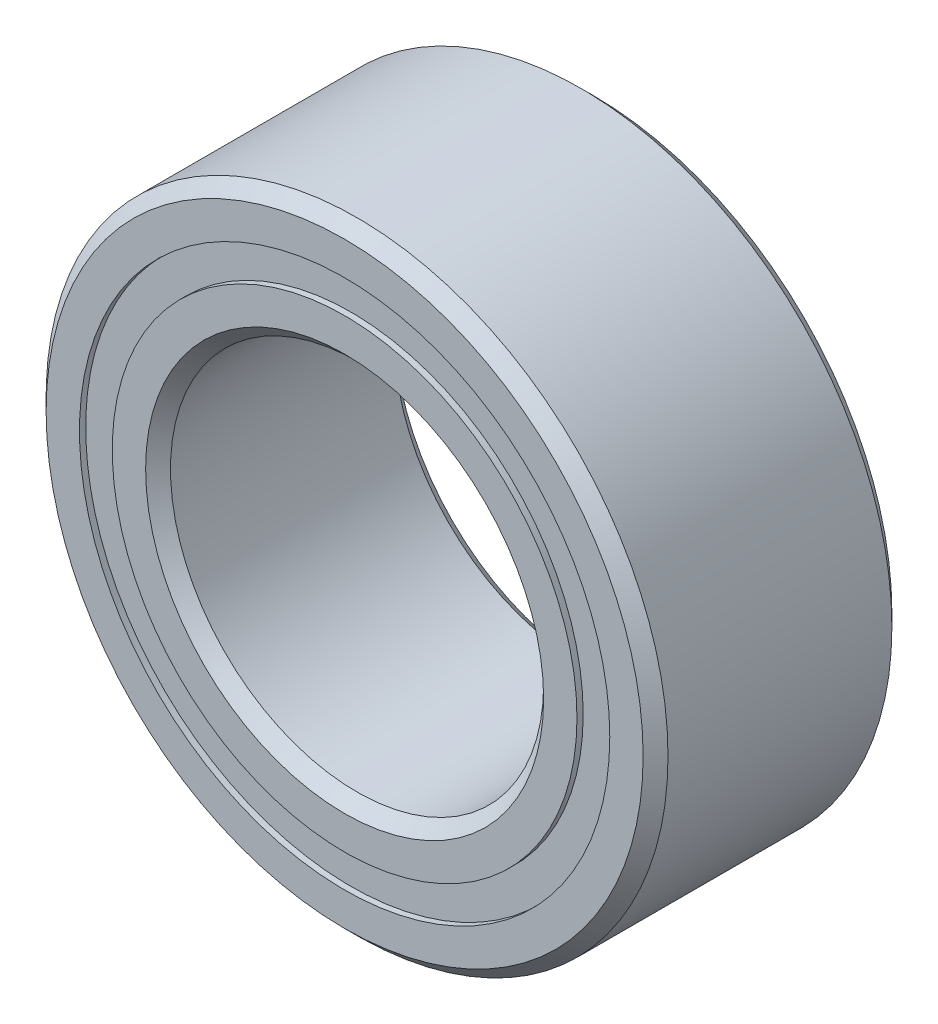
SolidWorks part; units mm, degrees
material "Cast Alloy Steel"
ref_plane "Front Plane" through (0, 0, 0) normal (0, 0, 1) x (1, 0, 0)
ref_plane "Top Plane" through (0, 0, 0) normal (0, 1, 0) x (1, 0, 0)
ref_plane "Right Plane" through (0, 0, 0) normal (1, 0, 0) x (0, 0, -1)
sketch "Sketch1" plane through (0, 0, 0) normal (1, 0, 0) x (0, 0, -1)
  line L0 (-1.5875, 0) -> (1.5875, 0) construction
  line L1 (0, 3.9688) -> (0, -3.9688) construction
  line L2 (1.4288, 3.9687) -> (-1.4288, 3.9687)
  line L3 (-1.4288, 3.9687) -> (-1.5875, 3.81)
  line L4 (-1.5875, 3.81) -> (-1.5875, 3.3843)
  line L5 (-1.5875, 3.3843) -> (-0.7056, 3.3843)
  line L6 (1.5875, 3.3843) -> (0.7056, 3.3843)
  line L7 (1.5875, 3.81) -> (1.5875, 3.3843)
  line L8 (1.4288, 3.9687) -> (1.5875, 3.81)
  line L9 (0, 3.9688) -> (0, 3.175) construction
  line L10 (0, 3.175) -> (0, 2.3813) construction
  arc A0 (-0.7056, 3.3843) -> (0.7056, 3.3843) centre (0, 3.175) cw
  point P14 (0, 2.3813)
  dimension "D3" = 1.4111
  dimension "D1" = 45
  dimension "Width" = 3.175
  dimension "OD" = 7.9375
  dimension "D2" = 0.1588
  dimension "Shaft Dia" = 4.7625
  dimension "D4" = 0.2093
revolve "Revolve1" add sketch "Sketch1" angle 360 about L0
sketch "Sketch3" plane through (0, 0, 0) normal (1, 0, 0) x (0, 0, -1)
  line L0 (-0.7056, 2.9657) -> (-1.5875, 2.9657)
  line L1 (-1.5875, 3.81) -> (-1.5875, 3.3843) construction
  line L2 (-1.4288, 3.9687) -> (-1.5875, 3.81) construction
  line L3 (-1.5875, 2.9657) -> (-1.5875, 2.54)
  line L5 (-1.5875, 2.54) -> (-1.4288, 2.3812)
  line L6 (-1.4288, 2.3812) -> (1.4288, 2.3813)
  line L7 (1.4288, 3.9687) -> (1.4288, -3.9687) construction
  line L8 (1.4288, 2.3813) -> (1.5875, 2.54)
  line L9 (1.5875, -3.81) -> (1.5875, 3.81) construction
  line L10 (1.5875, 2.54) -> (1.5875, 2.9657)
  line L11 (1.5875, 2.9657) -> (0.7056, 2.9657)
  line L12 (0, 3.9688) -> (0, -3.9688) construction
  line L13 (1.4288, 3.9687) -> (1.5875, 3.81) construction
  arc A1 (0.7056, 2.9657) -> (-0.7056, 2.9657) centre (0, 3.175) cw
  arc A2 (0.7056, 3.3843) -> (-0.7056, 3.3843) centre (0, 3.175) ccw construction
revolve "Revolve3" add sketch "Sketch3" angle 360 about L0
sketch "Sketch4" plane through (0, 0, 0) normal (1, 0, 0) x (0, 0, -1)
  line L0 (-0.736, 3.175) -> (0.736, 3.175)
  arc A2 (-0.736, 3.175) -> (0.736, 3.175) centre (0, 3.175) cw
  arc A3 (0.7056, 3.3843) -> (-0.7056, 3.3843) centre (0, 3.175) ccw construction
revolve "Revolve4" add sketch "Sketch4" angle 360 about L0
ref_axis "Axis1" through (0, 0, -1.5875) along (0, 0, 1)
pattern_circular "CirPattern1" count 12 every 30 about axis through (0, 0, -1.5875) along (0, 0, 1) of bodies 104
sketch "Sketch5" plane through (0, 0, 0) normal (1, 0, 0) x (0, 0, -1)
  line L0 (-1.5875, 3.3843) -> (-0.7056, 3.3843) construction
  line L1 (-1.5081, 3.3843) -> (-0.736, 3.3843)
  line L2 (-1.5081, 3.3843) -> (-1.5081, 2.9657)
  line L3 (-1.5081, 2.9657) -> (-0.736, 2.9657)
  line L4 (-0.736, 3.3843) -> (-0.736, 2.9657)
  line L5 (-0.7056, 2.9657) -> (-1.5875, 2.9657) construction
  line L6 (1.5875, 3.3843) -> (0.7056, 3.3843) construction
  line L7 (1.5081, 3.3843) -> (0.736, 3.3843)
  line L8 (1.5081, 3.3843) -> (1.5081, 2.9657)
  line L9 (1.5081, 2.9657) -> (0.736, 2.9657)
  line L10 (0.736, 3.3843) -> (0.736, 2.9657)
  line L11 (1.5875, 2.9657) -> (0.7056, 2.9657) construction
  line L12 (-1.4288, 3.9687) -> (-1.5875, 3.81) construction
  point P18 (-1.5081, 3.8894)
revolve "Revolve5" add sketch "Sketch5" angle 360 about L0
equation "\"D2@Sketch1\" = \"Width@Sketch1\"*.05"
equation "\"D3@Sketch1\" = \"Width@Sketch1\"/2.25"
equation "\"D4@Sketch1\" = (((\"OD@Sketch1\"-\"Width@Sketch1\")/2)/3.25)/3.5"
equation "\"D2@CirPattern1\" = 360/\"Balls@CirPattern1\""
